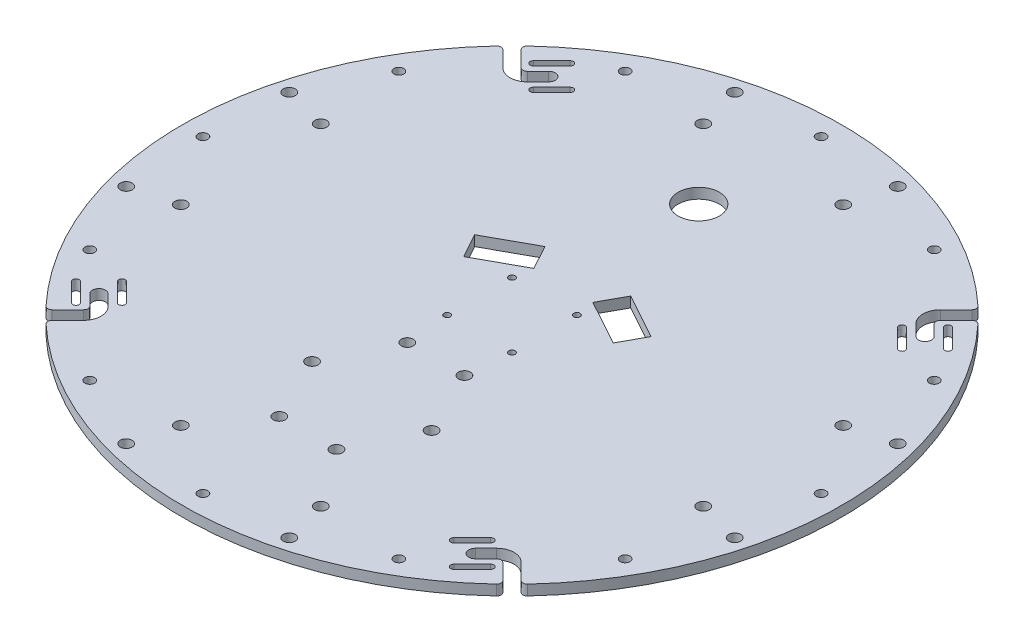
SolidWorks part; units mm, degrees
ref_plane "Front Plane" through (0, 0, 0) normal (0, 0, 1) x (1, 0, 0)
ref_plane "Top Plane" through (0, 0, 0) normal (0, 1, 0) x (1, 0, 0)
ref_plane "Right Plane" through (0, 0, 0) normal (1, 0, 0) x (0, 0, -1)
sketch "Sketch1" plane through (0, 0, 0) normal (0, 1, 0) x (1, 0, 0)
  circle A0 centre (0, 0) radius 152.4
  dimension "D1" = 304.8
extrude "Boss-Extrude1" add sketch "Sketch1" along normal blind 4.7625
sketch "Sketch2" plane through (0, 4.7625, 0) normal (0, 1, 0) x (1, 0, 0)
  circle A0 centre (0, 0) radius 142.875 construction
  point P3 (0, -142.875)
  dimension "D1" = 285.75
hole_wizard "#8 Clearance Hole1" positions "Sketch3" profile "Sketch4" hole size "#8" standard "ANSI Inch" end condition through all
sketch "Sketch3" plane through (0, 4.7625, 0) normal (0, 1, 0) x (1, 0, 0)
  point P0 (0, -142.875)
sketch "Sketch4" plane through (0, 4.7625, 142.875) normal (1, 0, 0) x (0, 0, 1)
  line L0 (0, 0) -> (0, 4.7625)
  line L1 (0, 4.7625) -> (2.2479, 4.7625)
  line L2 (2.2479, 4.7625) -> (2.2479, 0)
  line L5 (2.2479, 0) -> (0, 0)
  line L11 (0, -6.35) -> (0, 107.95) construction
  dimension "Thru Hole Dia." = 4.4958
  dimension "Thru Hole Depth" = 4.7625
pattern_circular "CirPattern1" count 12 over 360 about axis through (0, 4.7625, 0) along (0, -1, 0) of "#8 Clearance Hole1"
sketch "Sketch5" plane through (0, 4.7625, 0) normal (0, 1, 0) x (1, 0, 0)
  line L1 (-15, 15) -> (15, 15) construction
  line L2 (-15, 15) -> (-15, -15) construction
  line L3 (-15, -15) -> (15, -15) construction
  line L4 (15, 15) -> (15, -15) construction
  line L5 (-15, 15) -> (15, -15) construction
  line L6 (-15, -15) -> (15, 15) construction
  circle A0 centre (0, 0) radius 26
  circle A1 centre (0, 0) radius 27
  point P0 (0, 0)
  dimension "D3" = 52
  dimension "D1" = 30
  dimension "D2" = 30
  dimension "D4" = 1
hole_wizard "M2.5 Clearance Hole1" positions "Sketch6" profile "Sketch7" hole size "M2.5" standard "ANSI Metric" end condition through all
sketch "Sketch6" plane through (0, 4.7625, 0) normal (0, 1, 0) x (1, 0, 0)
  point P0 (-15, -15)
  point P3 (-15, 15)
  point P6 (15, 15)
  point P9 (15, -15)
sketch "Sketch7" plane through (-15, 4.7625, 15) normal (1, 0, 0) x (0, 0, 1)
  line L0 (0, 0) -> (0, 4.7625)
  line L1 (0, 4.7625) -> (1.45, 4.7625)
  line L2 (1.45, 4.7625) -> (1.45, 0)
  line L5 (1.45, 0) -> (0, 0)
  line L11 (0, -6.35) -> (0, 107.95) construction
  dimension "Thru Hole Dia." = 2.9
  dimension "Thru Hole Depth" = 4.7625
extrude "Cut-Extrude2" [suppressed] cut sketch "Sketch5" against normal blind 1
sketch "Sketch8" plane through (0, 4.7625, 0) normal (0, 1, 0) x (1, 0, 0)
  line L0 (0, 0) -> (71.4375, -123.7334) construction
  line L1 (71.4375, -123.7334) -> (123.7334, -71.4375) construction
  line L3 (0, 0) -> (97.5854, -97.5854) construction
  line L4 (105.6418, -109.8844) -> (95.4641, -99.7068)
  line L5 (95.4641, -99.7068) -> (86.9788, -108.192)
  line L6 (86.9788, -108.192) -> (82.7362, -103.9494)
  line L7 (82.7362, -103.9494) -> (95.4641, -91.2215)
  line L8 (95.4641, -91.2215) -> (109.8844, -105.6418)
  line L9 (109.8844, -105.6418) -> (105.6418, -109.8844)
  line L10 (87.3324, -114.2024) -> (95.8177, -105.7172) construction
  line L11 (86.2717, -113.1418) -> (94.757, -104.6565)
  line L12 (88.3931, -115.2631) -> (96.8783, -106.7778)
  line L13 (84.8575, -106.0707) -> (97.5854, -93.3428) construction
  line L14 (76.7258, -103.5958) -> (85.2111, -95.1106) construction
  line L15 (77.7864, -104.6565) -> (86.2717, -96.1712)
  line L16 (75.6651, -102.5352) -> (84.1504, -94.0499)
  circle A0 centre (0, 0) radius 152.4 construction
  arc A1 (86.2717, -113.1418) -> (88.3931, -115.2631) centre (87.3324, -114.2024) ccw
  arc A2 (96.8783, -106.7778) -> (94.757, -104.6565) centre (95.8177, -105.7172) ccw
  arc A3 (77.7864, -104.6565) -> (75.6651, -102.5352) centre (76.7258, -103.5958) cw
  arc A4 (84.1504, -94.0499) -> (86.2717, -96.1712) centre (85.2111, -95.1106) cw
  point P9 (91.575, -109.9598)
  point P27 (80.9684, -99.3532)
  dimension "D6" = 1.5
  dimension "D7" = 2.5
  dimension "D1" = 3
  dimension "D2" = 6
  dimension "D3" = 6
  dimension "D4" = 12
  dimension "D5" = 12
  dimension "D8" = 3
extrude "Cut-Extrude1" cut sketch "Sketch8" against normal through all
fillet "Fillet1" 2 edges at (82.7362, 2.3813, 103.9494) (86.9788, 2.3813, 108.192) type full round first side face at (89.1002, 2.3813, 97.5854) second side face at (91.2215, 2.3813, 103.9494) middle face at (84.8575, 2.3813, 106.0707)
fillet "Fillet2" radius 2 3 edges at (109.8635, 2.3813, 105.6209) (105.6209, 2.3813, 109.8635) (95.4641, 2.3813, 99.7068)
fillet "Fillet3" radius 8 1 edges at (95.4641, 2.3813, 91.2215)
pattern_circular "CirPattern2" count 4 over 360 about axis through (0, 4.7625, 0) along (0, -1, 0) of "Cut-Extrude1", "Fillet1", "Fillet2", "Fillet3"
sketch "Sketch9" plane through (0, 4.7625, 0) normal (0, 1, 0) x (1, 0, 0)
  line L0 (-13.2, -35.21) -> (-13.2, -94.36) construction
  line L1 (-13.2, -94.36) -> (13.2, -94.36) construction
  line L2 (13.2, -94.36) -> (13.2, -35.21) construction
  line L3 (13.2, -35.21) -> (-13.2, -35.21) construction
  line L5 (0, -94.36) -> (0, -35.21) construction
  line L7 (27.62, -64.79) -> (-27.62, -64.79) construction
  point P0 (-13.2, -35.21)
  point P1 (-27.62, -64.79)
  point P2 (-13.2, -94.36)
  point P3 (13.2, -94.36)
  point P4 (27.62, -64.79)
  point P5 (13.2, -35.21)
  point P8 (0, -64.79)
  dimension "D1" = 13.2
  dimension "D2" = 27.62
  dimension "D3" = 35.21
  dimension "D4" = 64.79
  dimension "D5" = 94.36
hole_wizard "M5 Clearance Hole1" positions "Sketch10" profile "Sketch11" hole size "M5" standard "ANSI Metric" end condition through all
sketch "Sketch10" plane through (0, 4.7625, 0) normal (0, 1, 0) x (1, 0, 0)
  point P0 (-13.2, -35.21)
  point P3 (13.2, -35.21)
  point P6 (27.62, -64.79)
  point P9 (13.2, -94.36)
  point P12 (-13.2, -94.36)
  point P15 (-27.62, -64.79)
sketch "Sketch11" plane through (-13.2, 4.7625, 35.21) normal (1, 0, 0) x (0, 0, 1)
  line L0 (0, 0) -> (0, 4.7625)
  line L1 (0, 4.7625) -> (2.75, 4.7625)
  line L2 (2.75, 4.7625) -> (2.75, 0)
  line L5 (2.75, 0) -> (0, 0)
  line L11 (0, -6.35) -> (0, 107.95) construction
  dimension "Thru Hole Dia." = 5.5
  dimension "Thru Hole Depth" = 4.7625
sketch "Sketch12" plane through (0, 4.7625, 0) normal (0, 1, 0) x (1, 0, 0)
  line L0 (0, -142.875) -> (71.4375, -123.7334) construction
  line L1 (71.4375, -123.7334) -> (0, 0) construction
  line L2 (0, 0) -> (0, -142.875) construction
  line L3 (0, 0) -> (35.7187, -133.3042) construction
  line L4 (32.3541, -120.7472) -> (37.6858, -140.6452) construction
  line L5 (24.4133, -149.0674) -> (53.3911, -141.3028)
  line L6 (24.4133, -149.0674) -> (16.6488, -120.0896)
  line L7 (53.3911, -141.3028) -> (45.6265, -112.325)
  line L8 (16.6488, -120.0896) -> (45.6265, -112.325)
  line L9 (24.4133, -149.0674) -> (45.6265, -112.325) construction
  line L10 (53.3911, -141.3028) -> (16.6488, -120.0896) construction
  point P7 (37.6858, -140.6452)
  point P8 (32.3541, -120.7472)
  point P12 (35.0199, -130.6962)
  dimension "D1" = 20.6
  dimension "D2" = 13
  dimension "D3" = 30
  dimension "D4" = 30
hole_wizard "M5 Clearance Hole2" positions "Sketch13" profile "Sketch14" hole size "M5" standard "ANSI Metric" end condition through all
sketch "Sketch13" plane through (0, 4.7625, 0) normal (0, 1, 0) x (1, 0, 0)
  point P0 (32.3541, -120.7472)
  point P3 (37.6858, -140.6452)
sketch "Sketch14" plane through (32.3541, 4.7625, 120.7472) normal (1, 0, 0) x (0, 0, 1)
  line L0 (0, 0) -> (0, 4.7625)
  line L1 (0, 4.7625) -> (2.75, 4.7625)
  line L2 (2.75, 4.7625) -> (2.75, 0)
  line L5 (2.75, 0) -> (0, 0)
  line L11 (0, -6.35) -> (0, 107.95) construction
  dimension "Thru Hole Dia." = 5.5
  dimension "Thru Hole Depth" = 4.7625
pattern_circular "CirPattern3" count 12 over 360 about axis through (0, 4.7625, 0) along (0, -1, 0) skipping 2, 5, 8, 11 of "M5 Clearance Hole2"
sketch "Sketch15" plane through (0, 4.7625, 0) normal (0, 1, 0) x (1, 0, 0)
  circle A0 centre (-1.2422, 87.5723) radius 9.525
  dimension "D1" = 19.05
extrude "Cut-Extrude3" cut sketch "Sketch15" against normal up to next
sketch "Sketch16" plane through (0, 4.7625, 0) normal (0, 1, 0) x (1, 0, 0)
  line L0 (40.7696, 23.5328) -> (34.5655, 12.2325)
  line L1 (40.7696, 23.5328) -> (19.8215, 35.0338)
  line L2 (34.5655, 12.2325) -> (13.6174, 23.7334)
  line L3 (19.8215, 35.0338) -> (13.6174, 23.7334)
  line L4 (0, 0) -> (0, 44.804) construction
  line L5 (-19.8215, 35.0338) -> (-13.6174, 23.7334)
  line L6 (-34.5655, 12.2325) -> (-13.6174, 23.7334)
  line L7 (-40.7696, 23.5328) -> (-19.8215, 35.0338)
  line L8 (-40.7696, 23.5328) -> (-34.5655, 12.2325)
extrude "Cut-Extrude4" cut sketch "Sketch16" against normal up to next
